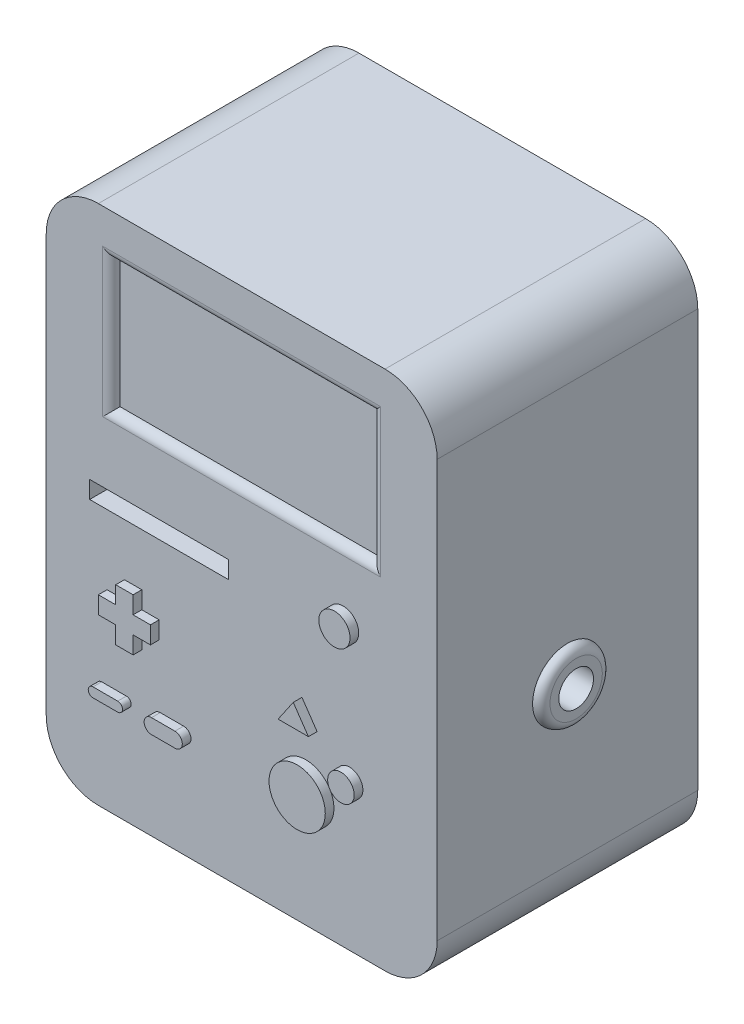
SolidWorks part; units mm, degrees
material "PET"
ref_plane "Front Plane" through (0, 0, 0) normal (0, 0, 1) x (1, 0, 0)
ref_plane "Top Plane" through (0, 0, 0) normal (0, 1, 0) x (1, 0, 0)
ref_plane "Right Plane" through (0, 0, 0) normal (1, 0, 0) x (0, 0, -1)
sketch "Sketch2" plane through (0, 0, 0) normal (0, 1, 0) x (1, 0, 0)
  line L1 (-57.15, -38.1) -> (57.15, -38.1)
  line L2 (-57.15, -38.1) -> (-57.15, 38.1)
  line L3 (-57.15, 38.1) -> (57.15, 38.1)
  line L4 (57.15, -38.1) -> (57.15, 38.1)
  line L5 (-57.15, -38.1) -> (57.15, 38.1) construction
  line L6 (-57.15, 38.1) -> (57.15, -38.1) construction
  point P0 (0, 0)
  dimension "D1" = 114.3
  dimension "D2" = 76.2
extrude "Boss-Extrude1" add sketch "Sketch2" along normal blind 152.4
sketch "Sketch3" plane through (0, 0, 38.1) normal (0, 0, 1) x (1, 0, 0)
  line L0 (-57.15, 152.4) -> (57.15, 152.4) construction
  line L1 (-38.1, 139.7) -> (38.1, 139.7)
  line L2 (-38.1, 139.7) -> (-38.1, 101.6)
  line L3 (-38.1, 101.6) -> (38.1, 101.6)
  line L4 (38.1, 139.7) -> (38.1, 101.6)
  line L5 (-38.1, 139.7) -> (38.1, 101.6) construction
  line L6 (-38.1, 101.6) -> (38.1, 139.7) construction
  line L7 (57.15, 152.4) -> (57.15, 0) construction
  point P0 (0, 120.65)
  dimension "D1" = 12.7
  dimension "D2" = 19.05
  dimension "D3" = 38.1
  dimension "D4" = 76.2
extrude "Cut-Extrude1" cut sketch "Sketch3" against normal blind 2.54
fillet "Fillet2" radius 15.24 4 edges at (57.15, 0, 0) (-57.15, 0, 0) (57.15, 152.4, 0) (-57.15, 152.4, 0)
sketch "Sketch4" plane through (0, 0, 38.1) normal (0, 0, 1) x (1, 0, 0)
  line L0 (-57.15, 137.16) -> (-57.15, 15.24) construction
  line L1 (-44.45, 81.28) -> (-3.81, 81.28)
  line L2 (-44.45, 81.28) -> (-44.45, 76.2)
  line L3 (-44.45, 76.2) -> (-3.81, 76.2)
  line L4 (-3.81, 81.28) -> (-3.81, 76.2)
  line L5 (-41.91, 0) -> (41.91, 0) construction
  dimension "D1" = 40.64
  dimension "D2" = 5.08
  dimension "D3" = 12.7
  dimension "D4" = 76.2
extrude "Cut-Extrude2" cut sketch "Sketch4" against normal blind 20.32
sketch "Sketch5" plane through (0, 0, 38.1) normal (0, 0, 1) x (1, 0, 0)
  circle A0 centre (29.6577, 81.7133) radius 4.5627
extrude "Boss-Extrude2" add sketch "Sketch5" along normal blind 2.54
sketch "Sketch6" plane through (0, 0, 38.1) normal (0, 0, 1) x (1, 0, 0)
  line L0 (-34.29, 60.96) -> (-34.29, 55.88)
  line L1 (-34.29, 55.88) -> (-39.37, 55.88)
  line L2 (-39.37, 55.88) -> (-39.37, 50.8)
  line L3 (-39.37, 50.8) -> (-34.29, 50.8)
  line L4 (-34.29, 50.8) -> (-34.29, 45.72)
  line L5 (-34.29, 45.72) -> (-29.21, 45.72)
  line L6 (-29.21, 45.72) -> (-29.21, 50.8)
  line L7 (-29.21, 50.8) -> (-24.13, 50.8)
  line L8 (-24.13, 50.8) -> (-24.13, 55.88)
  line L9 (-24.13, 55.88) -> (-29.21, 55.88)
  line L10 (-29.21, 55.88) -> (-29.21, 60.96)
  line L11 (-29.21, 60.96) -> (-34.29, 60.96)
  line L12 (-57.15, 137.16) -> (-57.15, 15.24) construction
  line L13 (-41.91, 0) -> (41.91, 0) construction
  dimension "D1" = 5.08
  dimension "D2" = 17.78
  dimension "D3" = 45.72
sketch "Sketch7" plane through (0, 0, 38.1) normal (0, 0, 1) x (1, 0, 0)
  line L0 (17.6172, 57.1253) -> (13.1812, 50.6614)
  line L1 (13.1812, 50.6614) -> (22.0531, 50.6614)
  line L2 (22.0531, 50.6614) -> (17.6172, 57.1253)
sketch "Sketch8" plane through (0, 0, 38.1) normal (0, 0, 1) x (1, 0, 0)
  circle A0 centre (31.5588, 42.5499) radius 3.8796
sketch "Sketch9" plane through (0, 0, 38.1) normal (0, 0, 1) x (1, 0, 0)
  circle A0 centre (18.7578, 33.678) radius 8.2187
sketch "Sketch10" plane through (0, 0, 38.1) normal (0, 0, 1) x (1, 0, 0)
  line L0 (-40.9377, 30.3827) -> (-33.7134, 30.3827) construction
  line L1 (-40.9377, 31.7769) -> (-33.7134, 31.7769)
  line L2 (-40.9377, 28.9885) -> (-33.7134, 28.9885)
  line L3 (-23.8275, 30.3827) -> (-16.9835, 30.3827) construction
  line L4 (-23.8275, 32.5373) -> (-16.9835, 32.5373)
  line L5 (-23.8275, 28.2281) -> (-16.9835, 28.2281)
  arc A0 (-40.9377, 31.7769) -> (-40.9377, 28.9885) centre (-40.9377, 30.3827) ccw
  arc A1 (-33.7134, 28.9885) -> (-33.7134, 31.7769) centre (-33.7134, 30.3827) ccw
  arc A2 (-23.8275, 32.5373) -> (-23.8275, 28.2281) centre (-23.8275, 30.3827) ccw
  arc A3 (-16.9835, 28.2281) -> (-16.9835, 32.5373) centre (-16.9835, 30.3827) ccw
  point P2 (-37.3256, 30.3827)
  point P7 (-20.4055, 30.3827)
sketch "Sketch11" plane through (-57.15, 0, 0) normal (-1, 0, 0) x (0, 0, 1)
  circle A0 centre (0, 61.3078) radius 10.1959
extrude "Boss-Extrude3" add sketch "Sketch11" along normal blind 2.54
sketch "Sketch12" plane through (-59.69, 0, 0) normal (-1, 0, 0) x (0, 0, 1)
  circle A0 centre (0, 61.3078) radius 5.08
  dimension "D1" = 10.16
extrude "Cut-Extrude8" cut sketch "Sketch12" against normal blind 15.24
mirror "Mirror1" about plane through (0, 0, 0) normal (1, 0, 0) of "Boss-Extrude3", "Cut-Extrude8"
sketch "Sketch13" plane through (0, 0, 0) normal (0, -1, 0) x (1, 0, 0)
  line L0 (-41.91, 38.1) -> (-41.91, -38.1) construction
  line L2 (-41.91, 38.1) -> (41.91, 38.1) construction
  circle A0 centre (-25.4, 0) radius 6.35
  circle A1 centre (25.4, 0) radius 6.35
  dimension "D3" = 12.7
  dimension "D1" = 50.8
  dimension "D2" = 16.51
  dimension "D4" = 38.1
extrude "Cut-Extrude9" cut sketch "Sketch13" against normal blind 15.24
fillet "Fillet3" radius 2.54 2 edges at (-59.69, 61.3078, 10.1959) (59.69, 61.3078, 10.1959)
fillet "Fillet4" radius 2.54 4 edges at (0, 101.6, 38.1) (-38.1, 120.65, 38.1) (38.1, 120.65, 38.1) (0, 139.7, 38.1)
extrude "Boss-Extrude4" add sketch "Sketch6" along normal blind 2.54
extrude "Boss-Extrude5" add sketch "Sketch7" along normal blind 2.54
extrude "Boss-Extrude6" add sketch "Sketch8" along normal blind 2.54
extrude "Boss-Extrude7" add sketch "Sketch10" along normal blind 2.54
extrude "Boss-Extrude8" add sketch "Sketch9" along normal blind 2.54
